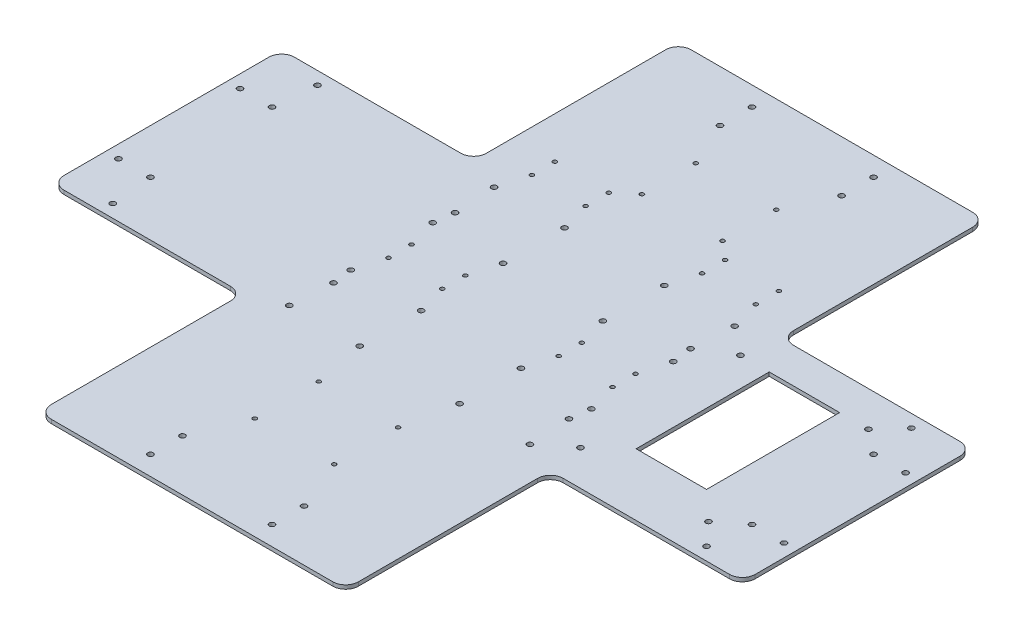
SolidWorks part; units mm, degrees
ref_plane "Front Plane" through (0, 0, 0) normal (0, 0, 1) x (1, 0, 0)
ref_plane "Top Plane" through (0, 0, 0) normal (0, 1, 0) x (1, 0, 0)
ref_plane "Right Plane" through (0, 0, 0) normal (1, 0, 0) x (0, 0, -1)
sketch "Sketch1" plane through (0, 0, 0) normal (0, 1, 0) x (1, 0, 0)
  line L0 (120, 250) -> (-120, 250)
  line L1 (-120, 250) -> (-120, 90)
  line L2 (-120, 90) -> (-270, 90)
  line L3 (-270, 90) -> (-270, -90)
  line L4 (0, 319.0603) -> (0, -214.0477) construction
  line L5 (-295.2994, 0) -> (181.6639, 0) construction
  line L6 (270, 90) -> (270, -90)
  line L7 (120, 90) -> (270, 90)
  line L8 (120, 250) -> (120, 90)
  line L9 (120, -250) -> (120, -90)
  line L10 (120, -90) -> (270, -90)
  line L11 (-120, -90) -> (-270, -90)
  line L12 (-120, -250) -> (-120, -90)
  line L13 (120, -250) -> (-120, -250)
  point P14 (0, 250)
  point P15 (-270, 0)
  point P16 (270, 0)
  point P20 (0, -250)
  dimension "D1" = 120
  dimension "D2" = 160
  dimension "150" = 150
  dimension "D3" = 90
extrude "Base" add sketch "Sketch1" along normal blind 3
fillet "Fillet1" radius 10 12 edges at (120, 1.5, -90) (270, 1.5, -90) (270, 1.5, 90) (120, 1.5, 90) (120, 1.5, 250) (-120, 1.5, 250) (-120, 1.5, 90) (-270, 1.5, 90) (-270, 1.5, -90) (-120, 1.5, -90) (-120, 1.5, -250) (120, 1.5, -250)
sketch "Sketch2" plane through (0, 3, 0) normal (0, 1, 0) x (1, 0, 0)
  line L0 (0, 268.1887) -> (0, -286.5172) construction
  line L1 (-278.1616, 0) -> (318.0529, 0) construction
  line L2 (110, 250) -> (-110, 250) construction
  line L3 (-270, 80) -> (-270, -80) construction
  circle A0 centre (-47.5, 235) radius 2.125
  circle A1 centre (-47.5, 210) radius 2.125
  circle A2 centre (-260, 47.5) radius 2.125
  circle A3 centre (-235, 47.5) radius 2.125
  circle A4 centre (-235, -47.5) radius 2.125
  circle A5 centre (-260, -47.5) radius 2.125
  circle A6 centre (260, -47.5) radius 2.125
  circle A7 centre (235, -47.5) radius 2.125
  circle A8 centre (235, 47.5) radius 2.125
  circle A9 centre (260, 47.5) radius 2.125
  circle A10 centre (47.5, 210) radius 2.125
  circle A11 centre (47.5, 235) radius 2.125
  circle A12 centre (47.5, -235) radius 2.125
  circle A13 centre (47.5, -210) radius 2.125
  circle A14 centre (-47.5, -210) radius 2.125
  circle A15 centre (-47.5, -235) radius 2.125
  dimension "D1" = 4.25
  dimension "D2" = 4.25
  dimension "D3" = 4.25
  dimension "D4" = 4.25
  dimension "D5" = 47.5
  dimension "D6" = 25
  dimension "D7" = 15
  dimension "D8" = 25
  dimension "D9" = 10
  dimension "D10" = 47.5
extrude "Armor Module Holes" cut sketch "Sketch2" against normal blind 3
sketch "Sketch3" plane through (0, 3, 0) normal (0, 1, 0) x (1, 0, 0)
  line L0 (-268.1887, 0) -> (424.969, 0) construction
  line L1 (0, 281.6655) -> (0, -321.0178) construction
  line L2 (-149.3232, 150) -> (229.1059, 150) construction
  line L3 (-149.3232, -150) -> (229.1059, -150) construction
  circle A0 centre (92, 47.5) radius 2.125
  circle A1 centre (92, -47.5) radius 2.125
  circle A2 centre (-92, -47.5) radius 2.125
  circle A3 centre (-92, 47.5) radius 2.125
  dimension "D2" = 4.25
  dimension "D1" = 150
  dimension "D3" = 47.5
  dimension "D4" = 92
extrude "Plates for Gimbal" cut sketch "Sketch3" against normal blind 3
sketch "Sketch6" plane through (0, 3, 0) normal (0, 1, 0) x (1, 0, 0)
  line L0 (-219.2229, 0) -> (231.3521, 0) construction
  line L1 (52.5596, 72.5) -> (282.564, 72.5) construction
  line L2 (52.5596, -72.5) -> (333.7759, -72.5) construction
  line L3 (92, 47.5) -> (235, 47.5) construction
  line L4 (166, 96.4976) -> (166, -82.3612) construction
  line L6 (138.5, 62.5) -> (193.5, 62.5)
  line L7 (138.5, 62.5) -> (138.5, -41.5)
  line L8 (138.5, -41.5) -> (193.5, -41.5)
  line L9 (193.5, 62.5) -> (193.5, -41.5)
  circle A2 centre (116, -62.5) radius 2.125
  circle A4 centre (216, -62.5) radius 2.125
  circle A5 centre (216, 62.5) radius 2.125
  circle A6 centre (116, 62.5) radius 2.125
  dimension "D3" = 10
  dimension "D4" = 50
  dimension "D6" = 4.25
  dimension "D1" = 72.5
  dimension "D2" = 72.5
  dimension "D9" = 74
  dimension "D12" = 55
  dimension "D13" = 27.5
  dimension "D14" = 10
  dimension "D15" = 104
extrude "Battery Mount" cut sketch "Sketch6" against normal blind 10
sketch "Sketch5" plane through (0, 3, 0) normal (0, 1, 0) x (1, 0, 0)
  line L0 (0, 63.8605) -> (0, -71.0696) construction
  line L1 (-72.0204, 0) -> (84.8823, 0) construction
  line L2 (120, -240) -> (120, -100) construction
  line L3 (-110, -250) -> (110, -250) construction
  line L4 (-158.9191, 72.5) -> (235.5165, 72.5) construction
  line L5 (193.5, 62.5) -> (138.5, 62.5) construction
  circle A0 centre (94, -32) radius 2.125
  circle A1 centre (94, -80) radius 2.125
  circle A2 centre (39, -32) radius 2.125
  circle A3 centre (39, -80) radius 2.125
  circle A4 centre (-39, -80) radius 2.125
  circle A5 centre (-39, -32) radius 2.125
  circle A6 centre (-94, -80) radius 2.125
  circle A7 centre (-94, -32) radius 2.125
  circle A8 centre (-94, 32) radius 2.125
  circle A9 centre (-94, 80) radius 2.125
  circle A10 centre (-39, 32) radius 2.125
  circle A11 centre (-39, 80) radius 2.125
  circle A12 centre (39, 80) radius 2.125
  circle A13 centre (39, 32) radius 2.125
  circle A14 centre (94, 80) radius 2.125
  circle A15 centre (94, 32) radius 2.125
  dimension "D1" = 4.25
  dimension "D2" = 4.25
  dimension "D5" = 4.25
  dimension "D6" = 4.25
  dimension "D9" = 10
  dimension "D3" = 48
  dimension "D4" = 26
  dimension "D7" = 55
  dimension "D8" = 170
extrude "Suspension Mount" cut sketch "Sketch5" against normal blind 10
sketch "Sketch7" plane through (0, 3, 0) normal (0, 1, 0) x (1, 0, 0)
  line L0 (-234.9459, 0) -> (256.0596, 0) construction
  line L1 (0, 229.7798) -> (0, -225.7367) construction
  line L2 (-120, -100) -> (-120, -240) construction
  circle A0 centre (-232, -80) radius 2.125
  circle A1 centre (-232, 80) radius 2.125
  circle A2 centre (232, 80) radius 2.125
  circle A3 centre (232, -80) radius 2.125
  dimension "D1" = 4.25
  dimension "D2" = 80
  dimension "D3" = 112
extrude "Outer Board Mount" cut sketch "Sketch7" against normal blind 10
sketch "Sketch8" plane through (0, 3, 0) normal (0, 1, 0) x (1, 0, 0)
  line L0 (0, 44.5441) -> (0, -214.63) construction
  line L1 (-110, -250) -> (110, -250) construction
  circle A0 centre (-31, -120) radius 1.575
  circle A1 centre (-31, -170) radius 1.575
  circle A2 centre (31, -170) radius 1.575
  circle A3 centre (31, -120) radius 1.575
  dimension "D1" = 3.15
  dimension "D4" = 3.15
  dimension "D2" = 31
  dimension "D3" = 130
  dimension "D5" = 31
  dimension "D6" = 80
extrude "RFID" cut sketch "Sketch8" against normal blind 10
sketch "Sketch9" plane through (0, 3, 0) normal (0, 1, 0) x (1, 0, 0)
  line L0 (0, 0) -> (0, 254.038) construction
  line L1 (110, 250) -> (-110, 250) construction
  circle A0 centre (-31.5, 175) radius 1.575
  circle A1 centre (-31.5, 133) radius 1.575
  circle A2 centre (31.5, 133) radius 1.575
  circle A3 centre (31.5, 175) radius 1.575
  dimension "D1" = 3.15
  dimension "D4" = 3.15
  dimension "D2" = 31.5
  dimension "D3" = 75
  dimension "D5" = 42
extrude "PMM" cut sketch "Sketch9" against normal blind 10
sketch "Sketch10" plane through (0, 3, 0) normal (0, 1, 0) x (1, 0, 0)
  line L0 (-154.9834, 0) -> (149.5927, 0) construction
  line L1 (0, 17.7647) -> (0, -17.2866) construction
  line L2 (-94, 32) -> (-39, 32) construction
  line L3 (-66.5, 32) -> (-66.5, 0) construction
  line L4 (-39, 80) -> (-39, 32) construction
  line L5 (-39, 56) -> (111.5999, 56) construction
  circle A0 centre (-87.5, 9) radius 1.575
  circle A1 centre (-45.5, 9) radius 1.575
  circle A2 centre (-45.5, -9) radius 1.575
  circle A3 centre (-87.5, -9) radius 1.575
  circle A4 centre (87.5, -9) radius 1.575
  circle A5 centre (45.5, -9) radius 1.575
  circle A6 centre (45.5, 9) radius 1.575
  circle A7 centre (87.5, 9) radius 1.575
  circle A8 centre (87.5, 103) radius 1.575
  circle A9 centre (45.5, 103) radius 1.575
  circle A10 centre (45.5, 121) radius 1.575
  circle A11 centre (87.5, 121) radius 1.575
  circle A12 centre (-87.5, 121) radius 1.575
  circle A13 centre (-45.5, 121) radius 1.575
  circle A14 centre (-45.5, 103) radius 1.575
  circle A15 centre (-87.5, 103) radius 1.575
  dimension "D1" = 3.15
  dimension "D2" = 3.15
  dimension "D3" = 9
  dimension "D4" = 9
  dimension "D5" = 42
  dimension "D6" = 42
extrude "Cut-Extrude2" cut sketch "Sketch10" against normal blind 10
